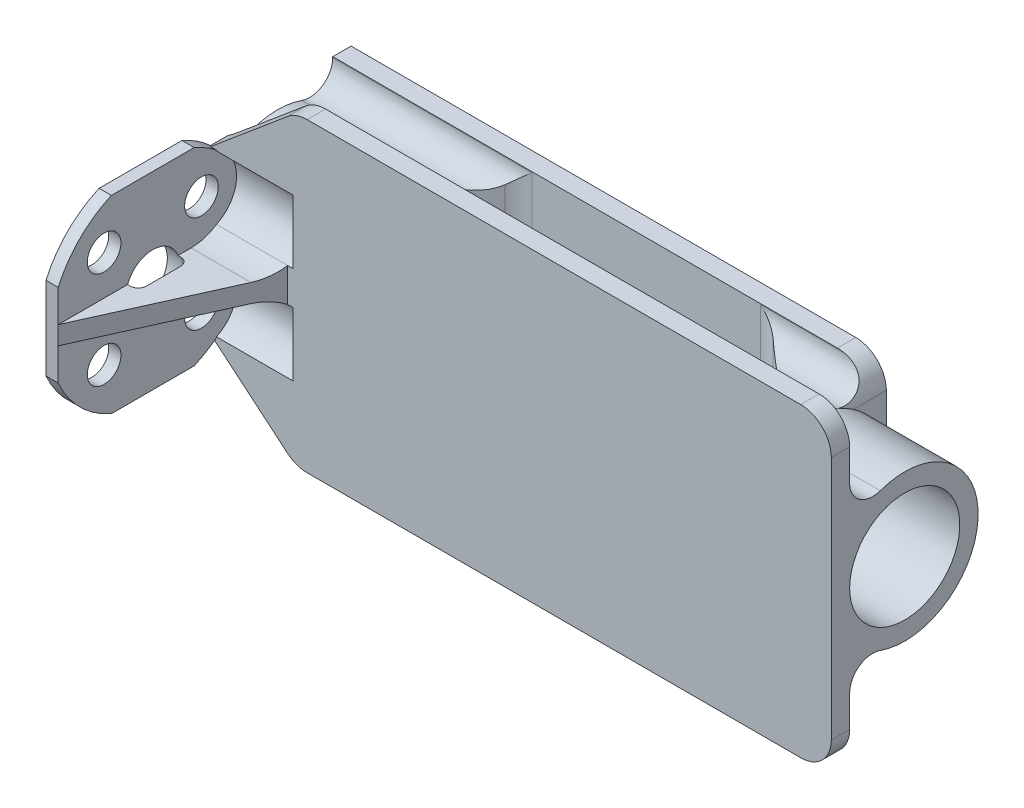
SolidWorks part; units mm, degrees
material "eSUN ePLA-LW"
ref_plane "Front Plane" through (0, 0, 0) normal (0, 0, 1) x (1, 0, 0)
ref_plane "Top Plane" through (0, 0, 0) normal (0, 1, 0) x (1, 0, 0)
ref_plane "Right Plane" through (0, 0, 0) normal (1, 0, 0) x (0, 0, -1)
sketch "Sketch1" plane through (0, 0, 0) normal (1, 0, 0) x (0, 0, -1)
  line L0 (0, 0) -> (-8.9643, 0) construction
  line L1 (-5.7823, 6.182) -> (-12.1463, 6.182)
  line L2 (-12.1463, -3.182) -> (-5.7823, -3.182) construction
  line L3 (-12.1463, -3.182) -> (-12.1463, 3.182) construction
  line L4 (-12.1463, 3.182) -> (-5.7823, 3.182) construction
  line L5 (-5.7823, -3.182) -> (-5.7823, 3.182) construction
  line L6 (-12.1463, -3.182) -> (-5.7823, 3.182) construction
  line L7 (-12.1463, 3.182) -> (-5.7823, -3.182) construction
  line L8 (-15.1463, 3.182) -> (-15.1463, 0)
  line L9 (-15.1463, 0) -> (-3.6, 0)
  circle A0 centre (0, 0) radius 3.6 construction
  circle A1 centre (-5.7823, 3.182) radius 3 construction
  arc A2 (-3.154, 1.7356) -> (-5.7823, 6.182) centre (-5.7823, 3.182) ccw
  circle A3 centre (-12.1463, 3.182) radius 3 construction
  arc A4 (-12.1463, 6.182) -> (-15.1463, 3.182) centre (-12.1463, 3.182) ccw
  arc A5 (-3.6, 0) -> (-3.154, 1.7356) centre (0, 0) cw
  point P5 (3.6, 0)
  point P19 (0, 0)
  point P20 (-3.6, 0)
  dimension "D1" = 7.2
  dimension "D2" = 6
  dimension "D3" = 9
extrude "Plate" add sketch "Sketch1" against normal blind 0.8
sketch "Sketch8" plane through (-0.8, 0, 0) normal (-1, 0, 0) x (0, 0, 1)
  circle A0 centre (8.9643, 0) radius 6.75
  dimension "D1" = 13.5
extrude "Cut-Extrude-Thin1" cut sketch "Sketch8" against normal through all both and the other way through all thin thin type one direction wall 15
sketch "Sketch6" plane through (0, 0, 0) normal (1, 0, 0) x (0, 0, -1)
  circle A0 centre (-12.1463, 3.182) radius 1.1
  circle A1 centre (-5.7823, 3.182) radius 1.1
  dimension "D1" = 2.2
extrude "Bolt Holes" cut sketch "Sketch6" against normal through all
sketch "Sketch7" plane through (0, 0, 0) normal (0, 1, 0) x (1, 0, 0)
  line L2 (5.2, -3.6) -> (-0.8, -3.6)
  line L3 (-0.8, -3.6) -> (-0.8, -15.1463)
  line L4 (-0.8, -15.1463) -> (0, -15.1463)
  line L6 (0, -15.1463) -> (5.2, -3.6)
  point P3 (42, -5)
  point P4 (30.4909, -7.0816)
  point P6 (5.2, -7.1117)
  point P11 (0, 0)
  dimension "D1" = 6
extrude "Rib" add sketch "Sketch7" along normal blind 0.6
sketch "Sketch9" plane through (-0.8, 0, 0) normal (-1, 0, 0) x (0, 0, 1)
  circle A0 centre (8.9643, 0) radius 1.75
  dimension "D1" = 3.5
extrude "Center Hole" cut sketch "Sketch9" against normal blind 1.5
fillet "Fillet1" radius 0.5 2 edges at (0.7, 0.3047, 7.241) (0.7, 0.3047, 10.6876)
sketch "Sketch13" plane through (0, 0, 0) normal (0, 0, 1) x (1, 0, 0)
  line L0 (5.2, 0) -> (0, 0) construction
  line L1 (5.2, 0) -> (40.2, 0)
  line L2 (5.2, 0) -> (5.2, 10)
  line L3 (5.2, 10) -> (40.2, 10)
  line L4 (40.2, 0) -> (40.2, 10)
  line L5 (5.2, 10) -> (-0.8, 4.9654)
  line L6 (-0.8, 4.9654) -> (-0.8, 0)
  line L7 (-0.8, 0) -> (5.2, 0)
  dimension "D1" = 20
  dimension "D2" = 35
  dimension "D3" = 50
extrude "Boss-Extrude3" add sketch "Sketch13" along normal blind 1.2 from vertex contours L6 L7 L2 L5 | L1 L4 L3 L2 region at (22.7, 5, 0) region at (2.5364, 3.8825, 0) starting at point (5.2, 0, 3.6)
sketch "Sketch14" plane through (0, 0, 0) normal (0, 0, 1) x (1, 0, 0)
  line L0 (-0.8, 0) -> (-7.9036, 0) construction
  line L1 (-0.8, 0) -> (34.2, 0)
  line L2 (-0.8, 0) -> (-0.8, 6)
  line L3 (-0.8, 6) -> (34.2, 6)
  line L4 (34.2, 0) -> (34.2, 6)
  point P6 (-1.6745, 2.0324)
  point P7 (-7.9036, 1.6035)
  point P8 (0, 0)
  dimension "D1" = 12
  dimension "D2" = 35
extrude "Boss-Extrude4" add sketch "Sketch14" against normal blind 1.2 from vertex contours L3 L4 L1 L2 starting at point (0, 0, -3.6)
sketch "Sketch2" plane through (0, 0, 0) normal (1, 0, 0) x (0, 0, -1)
  arc A0 (-3.6, 0) -> (3.6, 0) centre (0, 0) cw
  dimension "D1" = 180
extrude "Tube" add sketch "Sketch2" against normal up to surface (0.8 mm away) and the other way blind 40.2 thin up to face at (-0.8, 2.9833, 7.3005) thin type one direction reverse wall 1.2
fillet "Fillet5" radius 1.5 2 edges at (16.7, 3.1749, -3.6) (20.1, 3.1749, 3.6)
sketch "Sketch15" plane through (0, 0, 0) normal (0, 1, 0) x (1, 0, 0)
  line L0 (27.9097, -3.6) -> (11.4903, -3.6)
  line L1 (40.2, -3.6) -> (0, -3.6) construction
  line L2 (11.4903, -3.6) -> (7.2, 0)
  line L3 (7.2, 0) -> (11.4903, 3.6)
  line L5 (11.4903, 3.6) -> (27.9097, 3.6)
  line L6 (27.9097, 3.6) -> (32.2, 0)
  line L7 (32.2, 0) -> (27.9097, -3.6)
  line L8 (-0.8, 1.6) -> (-0.8, -1.6) construction
  line L9 (40.2, -1.6) -> (40.2, 4.8) construction
  line L10 (32.2, 0) -> (7.2, 0) construction
  point P7 (28.4553, 2.4844)
  point P14 (29.255, 3.8)
  point P17 (26.2886, -3.8)
  dimension "D1" = 8
  dimension "D2" = 8
  dimension "D3" = 40
extrude "Cut-Extrude1" cut sketch "Sketch15" along normal through all
fillet "Fillet6" radius 2 5 edges at (27.9097, 2.9698, 3.6) (27.9097, 2.9698, -3.6) (11.4903, 2.9698, -3.6) (11.4903, 2.9698, 3.6) (7.2, 4.2, 0)
sketch "Sketch16" plane through (0, 0, 0) normal (1, 0, 0) x (0, 0, -1)
  circle A0 centre (-5.7823, 3.182) radius 2.3
  dimension "D1" = 4.6
extrude "Cut-Extrude2" cut sketch "Sketch16" along normal blind 4
sketch "Sketch17" plane through (0, 0, 0) normal (1, 0, 0) x (0, 0, -1)
  circle A0 centre (-5.7823, 3.182) radius 1.1
  arc A1 (-4.8, 3.677) -> (-4.8, 2.6869) centre (-5.7823, 3.182) ccw construction
extrude "Cut-Extrude3" cut sketch "Sketch17" against normal through all
chamfer "Chamfer1" distance 1 angle 45 1 edges at (4, 3.182, 4.8)
fillet "Fillet8" radius 2 3 edges at (5.2, 10, 4.2) (34.2, 6, -4.2) (40.2, 10, 4.2)
fillet "Fillet9" radius 3 1 edges at (2.3298, 0.6, 4.8)
mirror "Mirror1" about plane through (0, 0, 0) normal (0, 1, 0) of bodies 116 104
